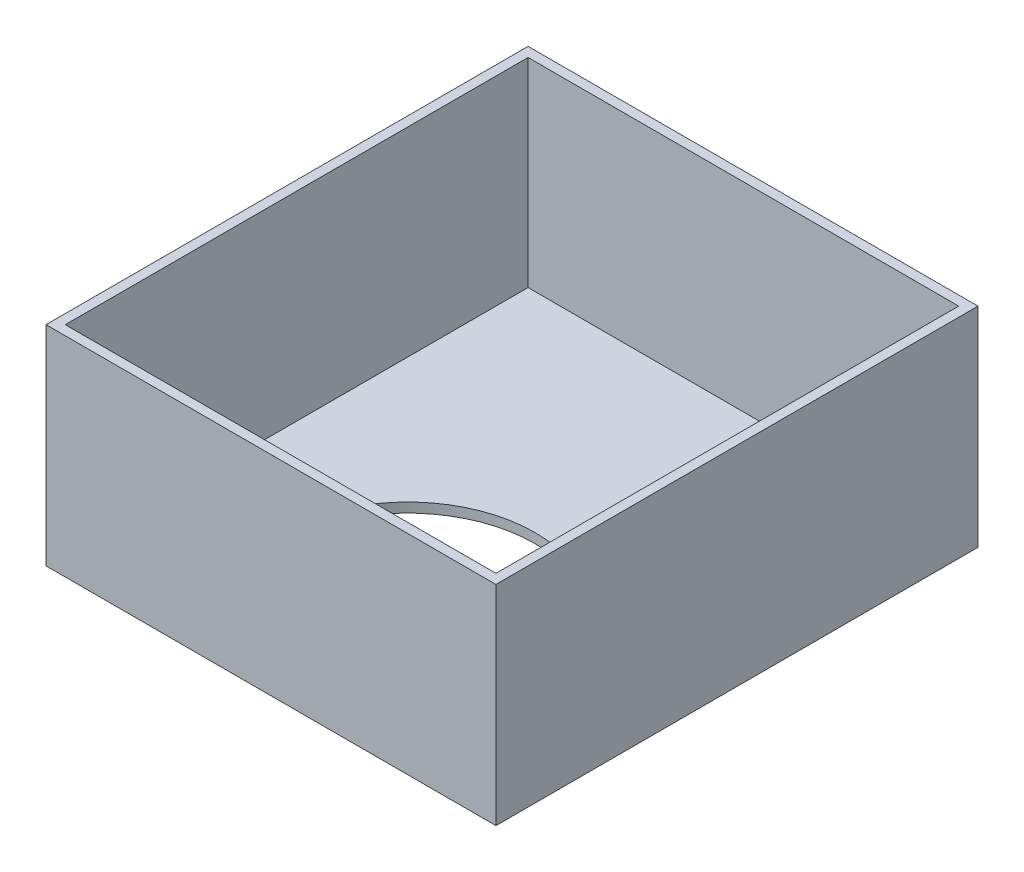
SolidWorks part; units mm, degrees
ref_plane "Front Plane" through (0, 0, 0) normal (0, 0, 1) x (1, 0, 0)
ref_plane "Top Plane" through (0, 0, 0) normal (0, 1, 0) x (1, 0, 0)
ref_plane "Right Plane" through (0, 0, 0) normal (1, 0, 0) x (0, 0, -1)
sketch "Sketch1" plane through (0, 0, 0) normal (0, 1, 0) x (1, 0, 0)
  line L1 (-45, 42.5) -> (45, 42.5)
  line L2 (-45, 42.5) -> (-45, -42.5)
  line L3 (-45, -42.5) -> (45, -42.5)
  line L4 (45, 42.5) -> (45, -42.5)
  line L5 (-45, 42.5) -> (45, -42.5) construction
  line L6 (-45, -42.5) -> (45, 42.5) construction
  point P0 (0, 0)
  dimension "D1" = 90
  dimension "D2" = 85
extrude "Boss-Extrude1" add sketch "Sketch1" along normal blind 3
sketch "Sketch2" plane through (0, 3, 0) normal (0, 1, 0) x (1, 0, 0)
  circle A0 centre (0, 0) radius 39.5
  dimension "D1" = 79
extrude "Cut-Extrude1" cut sketch "Sketch2" against normal blind 3
sketch "Sketch3" plane through (0, 3, 0) normal (0, 1, 0) x (1, 0, 0)
  line L0 (0, -40.15) -> (0, 40.15) construction
  line L1 (-40.15, 0) -> (40.15, 0) construction
  circle A0 centre (-42, 7) radius 1.5
  circle A1 centre (42, 7) radius 1.5
  circle A2 centre (42, -7) radius 1.5
  circle A3 centre (-42, -7) radius 1.5
  dimension "D1" = 3
  dimension "D2" = 42
  dimension "D3" = 7
extrude "Cut-Extrude2" cut sketch "Sketch3" against normal blind 3
sketch "Sketch4" plane through (0, 0, 0) normal (0, 1, 0) x (1, 0, 0)
  line L0 (-45, 28.701) -> (-45, 73.9136) construction
  line L2 (-45, 42.5) -> (-45, -42.5) construction
  line L7 (45, -42.5) -> (45, 42.5) construction
  line L8 (-70, 107.4337) -> (70, 107.4337)
  line L9 (-70, 107.4337) -> (-70, -42.5663)
  line L10 (-70, -42.5663) -> (70, -42.5663)
  line L11 (70, 107.4337) -> (70, -42.5663)
  dimension "D1" = 25
  dimension "D2" = 25
  dimension "D3" = 150
extrude "Boss-Extrude2" add sketch "Sketch4" along normal blind 70
sketch "Sketch5" plane through (0, 70, 0) normal (0, 1, 0) x (1, 0, 0)
  line L0 (70, 107.4337) -> (-70, 107.4337) construction
  line L1 (-67, 104.4337) -> (67, 104.4337)
  line L2 (-67, 104.4337) -> (-67, -39.5663)
  line L3 (-67, -39.5663) -> (67, -39.5663)
  line L4 (67, 104.4337) -> (67, -39.5663)
  line L5 (-70, 107.4337) -> (-70, -42.5663) construction
  line L6 (70, -42.5663) -> (70, 107.4337) construction
  line L7 (-70, -42.5663) -> (70, -42.5663) construction
  dimension "D1" = 3
  dimension "D2" = 3
  dimension "D3" = 3
  dimension "D4" = 3
extrude "Cut-Extrude6" cut sketch "Sketch5" against normal blind 67
sketch "Sketch6" plane through (0, 0, 0) normal (0, -1, 0) x (1, 0, 0)
  circle A0 centre (0, 0) radius 39.5
extrude "Cut-Extrude7" cut sketch "Sketch6" against normal blind 67
sketch "Sketch7" plane through (0, 0, 0) normal (0, -1, 0) x (1, 0, 0)
  line L2 (1.65, 0) -> (-1.65, 0) construction
  line L3 (0, -1.65) -> (0, 1.65) construction
  circle A4 centre (-42, 10) radius 1.375
  circle A5 centre (-42, -4) radius 1.375
  circle A6 centre (42, -4) radius 1.375
  circle A7 centre (42, 10) radius 1.375
  dimension "D5" = 2.75
  dimension "D6" = 2.75
  dimension "D1" = 10
  dimension "D2" = 42
  dimension "D3" = 4
  dimension "D4" = 42
extrude "Cut-Extrude8" cut sketch "Sketch7" against normal blind 10
sketch "Sketch8" plane through (0, 70, 0) normal (0, 1, 0) x (1, 0, 0)
  line L1 (-70, 107.4337) -> (70, 107.4337)
  line L2 (-70, 107.4337) -> (-70, -42.5663)
  line L3 (-70, -42.5663) -> (70, -42.5663)
  line L4 (70, 107.4337) -> (70, -42.5663)
extrude "Cut-Extrude9" cut sketch "Sketch8" against normal blind 5
